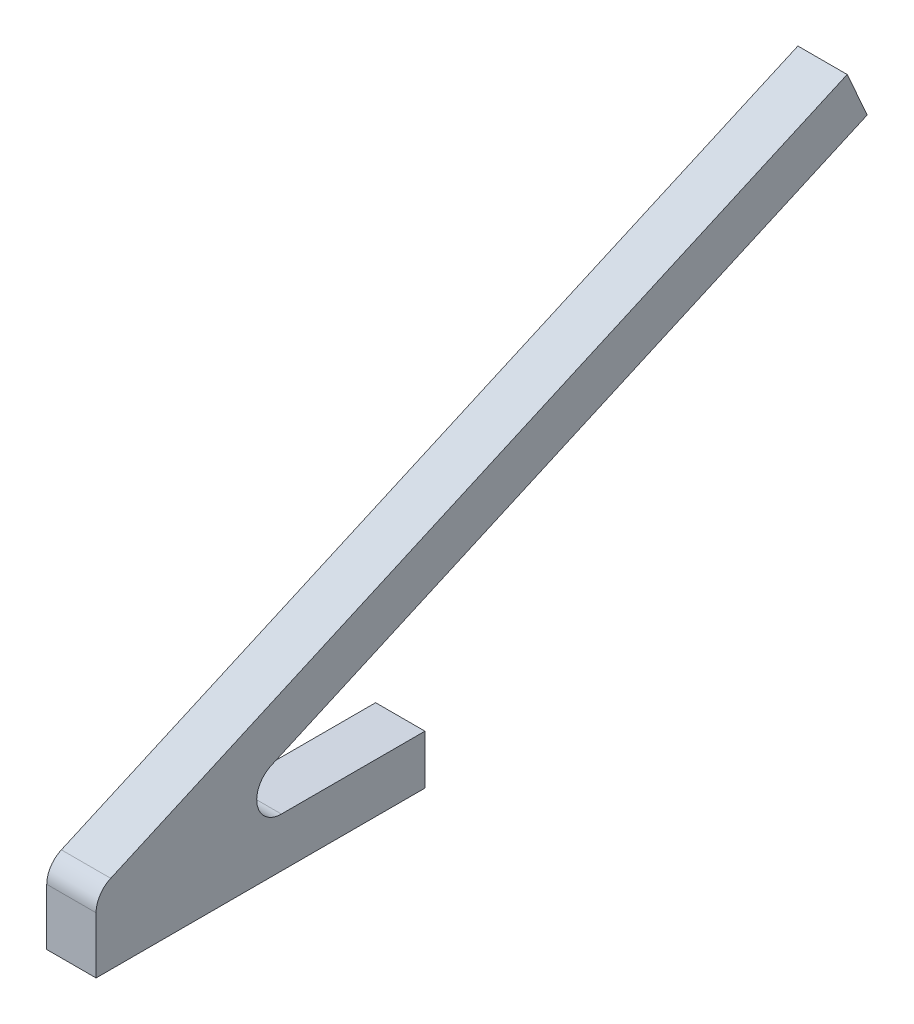
SolidWorks part; units mm, degrees
ref_plane "Front Plane" through (0, 0, 0) normal (0, 0, 1) x (1, 0, 0)
ref_plane "Top Plane" through (0, 0, 0) normal (0, 1, 0) x (1, 0, 0)
ref_plane "Right Plane" through (0, 0, 0) normal (1, 0, 0) x (0, 0, -1)
sketch "Sketch1" plane through (0, 0, 0) normal (1, 0, 0) x (0, 0, -1)
  line L0 (0, 0) -> (0, 8.8173)
  line L1 (0, 8.8173) -> (91.3545, 49.491)
  line L2 (91.3545, 49.491) -> (93.795, 44.0097)
  line L3 (93.795, 44.0097) -> (8.4237, 6)
  line L4 (8.4237, 6) -> (40, 6)
  line L5 (40, 6) -> (40, 0)
  line L6 (40, 0) -> (0, 0)
  dimension "D1" = 6
  dimension "D2" = 6
  dimension "D3" = 100
  dimension "D4" = 40
  dimension "D5" = 24
extrude "Boss-Extrude1" add sketch "Sketch1" along normal blind 6
fillet "Fillet1" radius 3 2 edges at (3, 8.8173, 0) (3, 6, -8.4237)
